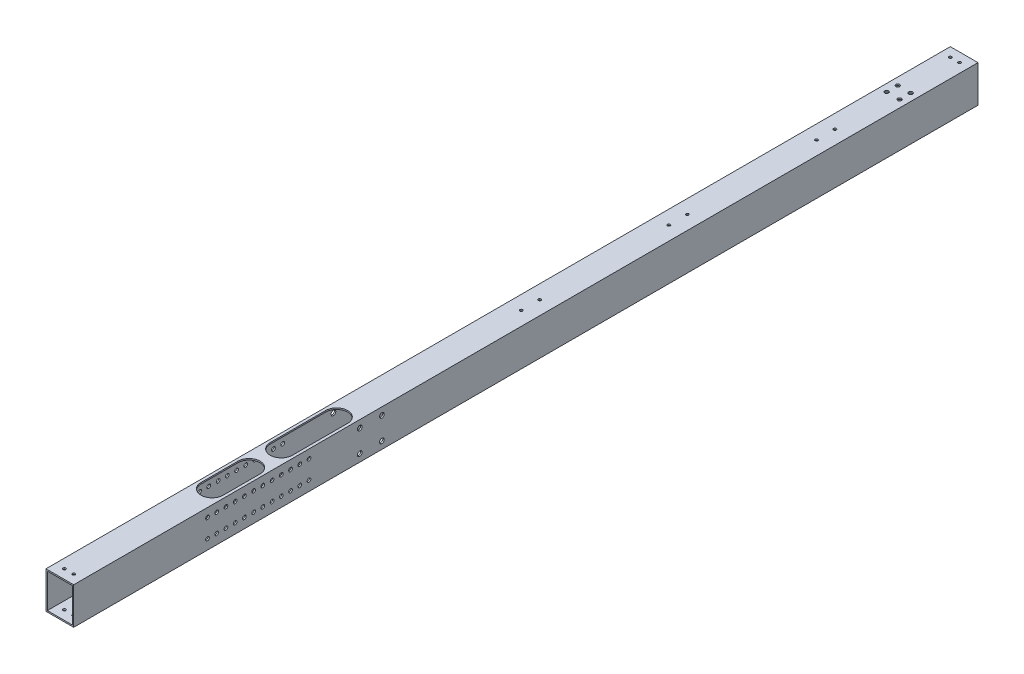
SolidWorks part; units mm, degrees
ref_plane "前视基准面" through (0, 0, 0) normal (0, 0, 1) x (1, 0, 0)
ref_plane "上视基准面" through (0, 0, 0) normal (0, 1, 0) x (1, 0, 0)
ref_plane "右视基准面" through (0, 0, 0) normal (1, 0, 0) x (0, 0, -1)
sketch "草图1" plane through (0, 0, 0) normal (0, 0, 1) x (1, 0, 0)
  line L0 (-13.5, 18.5) -> (13.5, 18.5)
  line L1 (-15, -20) -> (15, -20)
  line L2 (-15, -20) -> (-15, 20)
  line L3 (-15, 20) -> (15, 20)
  line L4 (15, -20) -> (15, 20)
  line L5 (-15, -20) -> (15, 20) construction
  line L6 (-15, 20) -> (15, -20) construction
  line L7 (13.5, -18.5) -> (13.5, 18.5)
  line L8 (-13.5, -18.5) -> (13.5, -18.5)
  line L9 (-13.5, -18.5) -> (-13.5, 18.5)
  point P0 (0, 0)
  dimension "D1" = 40
  dimension "D2" = 30
  dimension "D3" = 1.5
extrude "凸台-拉伸1" add sketch "草图1" along normal blind 980
sketch "草图2" plane through (0, 20, 0) normal (0, -1, 0) x (-1, 0, 0)
  line L0 (0, 0) -> (0, -50000) construction
  circle A0 centre (11, -65) radius 1.5
  circle A1 centre (-11, -65) radius 1.5
  circle A2 centre (11, -515) radius 1.5
  circle A3 centre (-11, -515) radius 1.5
  circle A4 centre (11, -105) radius 1.5
  circle A5 centre (-11, -105) radius 1.5
  dimension "D1" = 3
  dimension "D4" = 3
  dimension "D7" = 3
  dimension "D2" = 22
  dimension "D3" = 65
  dimension "D6" = 450
  dimension "D8" = 40
extrude "切除-拉伸1" [suppressed] cut sketch "草图2" along normal blind 1040
sketch "草图3" plane through (0, 20, 0) normal (0, -1, 0) x (-1, 0, 0)
  line L0 (0, 0) -> (0, -50000) construction
  line L2 (-16.5, -490) -> (49983.5, -490) construction
  line L3 (13.5, 0) -> (13.5, -980) construction
  line L4 (-13.5, 0) -> (-13.5, -980) construction
  line L5 (-15, 0) -> (15, 0) construction
  circle A0 centre (5, -10) radius 1.5
  circle A1 centre (-5, -10) radius 1.5
  circle A2 centre (-5, -970) radius 1.5
  circle A3 centre (5, -970) radius 1.5
  point P13 (13.5, -490)
  point P16 (-13.5, -490)
  dimension "D1" = 3
  dimension "D2" = 10
  dimension "D3" = 10
extrude "切除-拉伸2" cut sketch "草图3" along normal through all
sketch "草图4" plane through (0, 20, 0) normal (0, -1, 0) x (-1, 0, 0)
  line L1 (-8.2701, -787.5) -> (6.7299, -787.5) construction
  line L2 (-8.2701, -787.5) -> (-8.2701, -772.5) construction
  line L3 (-8.2701, -772.5) -> (6.7299, -772.5) construction
  line L4 (6.7299, -787.5) -> (6.7299, -772.5) construction
  line L5 (-8.2701, -787.5) -> (6.7299, -772.5) construction
  line L6 (-8.2701, -772.5) -> (6.7299, -787.5) construction
  line L7 (-0.7701, -780) -> (49999.2299, -780) construction
  line L8 (-0.7701, -840) -> (-0.7701, -50840) construction
  line L9 (15, -980) -> (-15, -980) construction
  circle A0 centre (-8.2701, -772.5) radius 3.25
  circle A1 centre (6.7299, -772.5) radius 3.25
  circle A2 centre (6.7299, -787.5) radius 3.25
  circle A3 centre (-8.2701, -787.5) radius 3.25
  point P0 (-0.7701, -780)
  dimension "D4" = 6.5
  dimension "D1" = 15
  dimension "D2" = 15
  dimension "D3" = 200
extrude "切除-拉伸3" cut sketch "草图4" along normal blind 21
sketch "草图5" plane through (0, 20, 0) normal (0, -1, 0) x (-1, 0, 0)
  line L0 (0, 0) -> (0, -50000) construction
  line L2 (0, -140) -> (0, -300) construction
  line L3 (0, -320) -> (0, -480) construction
  line L4 (15, 0) -> (-15, 0) construction
  circle A0 centre (0, -140) radius 1.5
  circle A1 centre (0, -160) radius 1.5
  circle A2 centre (0, -300) radius 1.5
  circle A3 centre (0, -320) radius 1.5
  circle A4 centre (0, -480) radius 1.5
  circle A5 centre (0, -460) radius 1.5
  dimension "D1" = 3
  dimension "D2" = 3
  dimension "D3" = 20
  dimension "D4" = 140
  dimension "D6" = 160
  dimension "D8" = 160
  dimension "D5" = 2
  dimension "D7" = 2
extrude "切除-拉伸4" cut sketch "草图5" along normal through all
sketch "草图8" plane through (0, -20, 0) normal (0, -1, 0) x (1, 0, 0)
  line L0 (0, 160) -> (0, 140) construction
  line L1 (7.5, 160) -> (7.5, 140)
  line L2 (-7.5, 160) -> (-7.5, 140)
  line L3 (0, 480) -> (0, 460) construction
  line L4 (7.5, 480) -> (7.5, 460)
  line L5 (-7.5, 480) -> (-7.5, 460)
  line L6 (0, 320) -> (0, 300) construction
  line L7 (7.5, 320) -> (7.5, 300)
  line L8 (-7.5, 320) -> (-7.5, 300)
  arc A0 (7.5, 160) -> (-7.5, 160) centre (0, 160) ccw
  arc A1 (-7.5, 140) -> (7.5, 140) centre (0, 140) ccw
  arc A2 (7.5, 480) -> (-7.5, 480) centre (0, 480) ccw
  arc A3 (-7.5, 460) -> (7.5, 460) centre (0, 460) ccw
  arc A4 (7.5, 320) -> (-7.5, 320) centre (0, 320) ccw
  arc A5 (-7.5, 300) -> (7.5, 300) centre (0, 300) ccw
  point P4 (0, 150)
  point P13 (0, 470)
  point P18 (0, 310)
  dimension "D1" = 7.5
  dimension "D2" = 7.5
  dimension "D3" = 7.5
extrude "切除-拉伸6" cut sketch "草图8" against normal blind 10
sketch "草图9" plane through (0, -20, 0) normal (0, -1, 0) x (1, 0, 0)
  line L0 (0, 980) -> (0, -135.6802) construction
  line L1 (-15, 980) -> (15, 980) construction
  circle A4 centre (10, 787.5) radius 1.6
  circle A5 centre (10, 774.5) radius 1.6
  circle A6 centre (-10, 774.5) radius 1.6
  circle A7 centre (-10, 787.5) radius 1.6
  dimension "D1" = 3.2
  dimension "D3" = 192.5
  dimension "D4" = 2
  dimension "D5" = 13
  dimension "D6" = 10
extrude "切除-拉伸7" cut sketch "草图9" against normal blind 10
pattern_linear "阵列(线性)1" count 6 spacing 13 along (0, 0, -1) of "切除-拉伸7"
sketch "草图10" plane through (-15, 0, 0) normal (-1, 0, 0) x (0, 0, 1)
  line L1 (0, 0) -> (664.4549, 0) construction
  line L2 (980, 20) -> (980, -20) construction
  circle A0 centre (646, 12) radius 2.55
  circle A1 centre (670, 12) radius 2.55
  circle A2 centre (646, -12) radius 2.55
  circle A3 centre (670, -12) radius 2.55
  dimension "D1" = 310
  dimension "D2" = 5.1
  dimension "D5" = 24
  dimension "D6" = 12
  dimension "D3" = 2
  dimension "D4" = 2
extrude "切除-拉伸8" cut sketch "草图10" against normal blind 51
sketch "草图11" plane through (-15, 0, 0) normal (-1, 0, 0) x (0, 0, 1)
  line L1 (980, 20) -> (980, -20) construction
  circle A0 centre (725, 10.6252) radius 2
  circle A1 centre (725, -9.3748) radius 2
  circle A2 centre (735, 10.6252) radius 2
  circle A3 centre (735, -9.3748) radius 2
  circle A4 centre (745, 10.6252) radius 2
  circle A5 centre (745, -9.3748) radius 2
  circle A6 centre (755, 10.6252) radius 2
  circle A7 centre (755, -9.3748) radius 2
  circle A8 centre (765, 10.6252) radius 2
  circle A9 centre (765, -9.3748) radius 2
  circle A10 centre (775, 10.6252) radius 2
  circle A11 centre (775, -9.3748) radius 2
  circle A12 centre (785, 10.6252) radius 2
  circle A13 centre (785, -9.3748) radius 2
  circle A14 centre (795, 10.6252) radius 2
  circle A15 centre (795, -9.3748) radius 2
  circle A16 centre (805, 10.6252) radius 2
  circle A17 centre (805, -9.3748) radius 2
  circle A18 centre (815, 10.6252) radius 2
  circle A19 centre (815, -9.3748) radius 2
  circle A20 centre (825, 10.6252) radius 2
  circle A21 centre (825, -9.3748) radius 2
  circle A22 centre (835, 10.6252) radius 2
  circle A23 centre (835, -9.3748) radius 2
  dimension "D1" = 4
  dimension "D2" = 2
  dimension "D4" = 145
  dimension "D3" = 12
extrude "切除-拉伸9" cut sketch "草图11" against normal blind 51
sketch "草图12" plane through (0, 20, 0) normal (0, 1, 0) x (1, 0, 0)
  line L0 (0, 0) -> (0, -98.6612) construction
  line L1 (15, 0) -> (-15, 0) construction
  circle A0 centre (-7, -65) radius 2.1
  circle A1 centre (-7, -77) radius 2.1
  circle A2 centre (7, -77) radius 2.1
  circle A3 centre (7, -65) radius 2.1
  dimension "D1" = 65
  dimension "D2" = 4.2
  dimension "D4" = 14
  dimension "D3" = 2
extrude "切除-拉伸10" cut sketch "草图12" against normal blind 10
sketch "草图13" plane through (0, -20, 0) normal (0, -1, 0) x (1, 0, 0)
  line L0 (0, 70.1408) -> (0, 99.7127) construction
  line L1 (-8.2089, 70.1408) -> (-8.2089, 99.7127)
  line L2 (8.2089, 70.1408) -> (8.2089, 99.7127)
  arc A0 (-8.2089, 70.1408) -> (8.2089, 70.1408) centre (0, 70.1408) ccw
  arc A1 (8.2089, 99.7127) -> (-8.2089, 99.7127) centre (0, 99.7127) ccw
  point P3 (0, 84.9268)
extrude "切除-拉伸11" cut sketch "草图13" against normal blind 10
sketch "草图14" plane through (0, 20, 0) normal (0, 1, 0) x (1, 0, 0)
  line L0 (0, -775) -> (0, -815) construction
  line L1 (12, -775) -> (12, -815)
  line L2 (-12, -775) -> (-12, -815)
  line L3 (15, -980) -> (-15, -980) construction
  arc A0 (12, -775) -> (-12, -775) centre (0, -775) ccw
  arc A1 (-12, -815) -> (12, -815) centre (0, -815) ccw
  point P3 (0, -795)
  dimension "D1" = 12
  dimension "D2" = 40
  dimension "D3" = 185
extrude "切除-拉伸12" cut sketch "草图14" against normal blind 10
sketch "草图15" plane through (0, -20, 0) normal (0, -1, 0) x (1, 0, 0)
  line L0 (0, 814.6625) -> (0, 610.1196) construction
  line L1 (0, 794.6625) -> (0, 590.1196) construction
  circle A0 centre (-7.5, 700) radius 1.6
  circle A1 centre (7.5, 700) radius 1.6
  circle A2 centre (10, 722.5) radius 1.6 construction
  circle A3 centre (-7.5, 680) radius 1.6
  circle A4 centre (7.5, 680) radius 1.6
  dimension "D1" = 3.2
  dimension "D2" = 15
  dimension "D3" = 22.5
  dimension "D5" = 20
  dimension "D4" = 2
extrude "切除-拉伸13" cut sketch "草图15" against normal blind 95
sketch "草图16" plane through (0, 20, 0) normal (0, 1, 0) x (1, 0, 0)
  line L0 (0, -633.404) -> (0, -752.1715) construction
  line L1 (0, -680) -> (0, -740) construction
  line L2 (12, -680) -> (12, -740)
  line L3 (-12, -680) -> (-12, -740)
  line L4 (15, -980) -> (15, 0) construction
  arc A0 (12, -680) -> (-12, -680) centre (0, -680) ccw
  arc A1 (-12, -740) -> (12, -740) centre (0, -740) ccw
  arc A2 (12, -775) -> (-12, -775) centre (0, -775) ccw construction
  point P5 (0, -710)
  dimension "D2" = 35
  dimension "D1" = 3
  dimension "D3" = 60
extrude "切除-拉伸14" cut sketch "草图16" against normal blind 5
equation "\"5。7\"=6"
